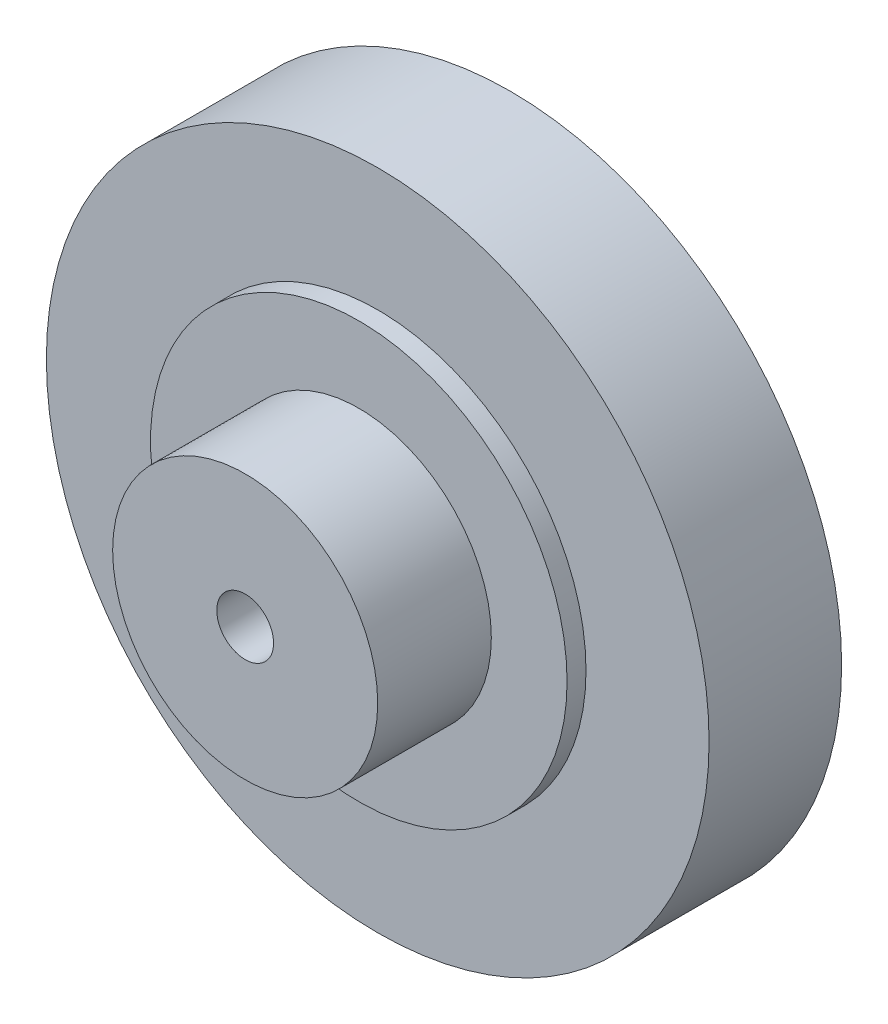
SolidWorks part; units mm, degrees
ref_plane "Plan de face" through (0, 0, 0) normal (0, 0, 1) x (1, 0, 0)
ref_plane "Plan de dessus" through (0, 0, 0) normal (0, 1, 0) x (1, 0, 0)
ref_plane "Plan de droite" through (0, 0, 0) normal (1, 0, 0) x (0, 0, -1)
sketch "Esquisse1" plane through (0, 0, 0) normal (0, 0, 1) x (1, 0, 0)
  circle A0 centre (0, 0) radius 35
extrude "Boss.-Extru.1" add sketch "Esquisse1" along normal blind 7 and the other way blind 7
sketch "Esquisse2" plane through (0, 0, 7) normal (0, 0, 1) x (1, 0, 0)
  circle A0 centre (0, 0) radius 22
extrude "Boss.-Extru.2" add sketch "Esquisse2" along normal blind 2
sketch "Esquisse3" plane through (0, 0, -7) normal (0, 0, -1) x (-1, 0, 0)
  circle A0 centre (0, 0) radius 22
extrude "Boss.-Extru.3" add sketch "Esquisse3" along normal blind 2
sketch "Esquisse4" plane through (0, 0, 9) normal (0, 0, 1) x (1, 0, 0)
  circle A0 centre (0, 0) radius 14
extrude "Boss.-Extru.4" add sketch "Esquisse4" along normal blind 12
sketch "Esquisse5" plane through (0, 0, -9) normal (0, 0, -1) x (-1, 0, 0)
  circle A0 centre (0, 0) radius 3
extrude "Enlèv. mat.-Extru.1" cut sketch "Esquisse5" against normal blind 59
